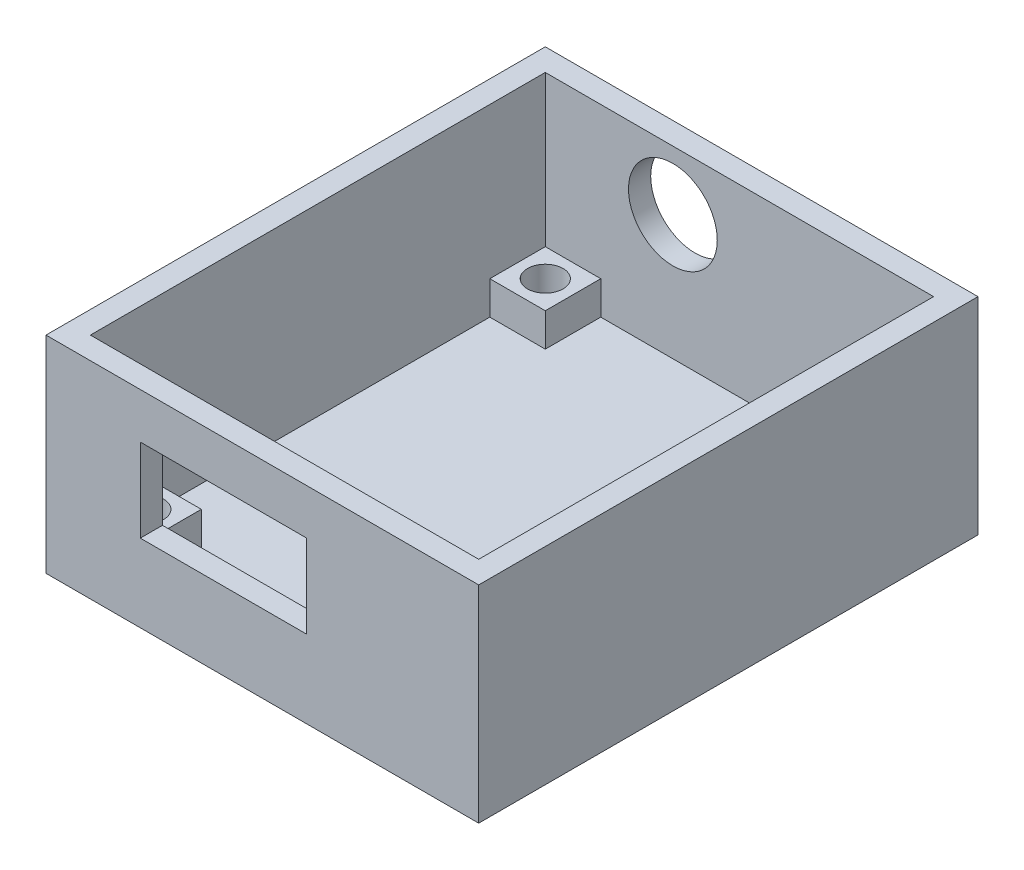
SolidWorks part; units mm, degrees
ref_plane "Front Plane" through (0, 0, 0) normal (0, 0, 1) x (1, 0, 0)
ref_plane "Top Plane" through (0, 0, 0) normal (0, 1, 0) x (1, 0, 0)
ref_plane "Right Plane" through (0, 0, 0) normal (1, 0, 0) x (0, 0, -1)
sketch "Sketch1" plane through (0, 0, 0) normal (0, 1, 0) x (1, 0, 0)
  line L1 (19.5, -22.5) -> (-19.5, -22.5)
  line L2 (19.5, -22.5) -> (19.5, 22.5)
  line L3 (19.5, 22.5) -> (-19.5, 22.5)
  line L4 (-19.5, -22.5) -> (-19.5, 22.5)
  line L5 (19.5, -22.5) -> (-19.5, 22.5) construction
  line L6 (19.5, 22.5) -> (-19.5, -22.5) construction
  point P0 (0, 0)
  dimension "D1" = 45
  dimension "D2" = 39
extrude "Body" add sketch "Sketch1" along normal blind 18.6
shell "Shell1" thickness 2 removed face at (0, 18.6, 0)
sketch "Sketch3" plane through (0, 2, 0) normal (0, 1, 0) x (1, 0, 0)
  line L0 (-1000, 0) -> (49000, 0) construction
  line L5 (-17.5, 20.5) -> (-12.5, 20.5)
  line L6 (-17.5, 20.5) -> (-17.5, 15.5)
  line L7 (-17.5, 15.5) -> (-12.5, 15.5)
  line L8 (-12.5, 20.5) -> (-12.5, 15.5)
  line L9 (0, -1000) -> (0, 49000) construction
  line L10 (12.5, 20.5) -> (12.5, 15.5)
  line L11 (17.5, 15.5) -> (12.5, 15.5)
  line L12 (17.5, 20.5) -> (17.5, 15.5)
  line L13 (17.5, 20.5) -> (12.5, 20.5)
  line L14 (17.5, -20.5) -> (12.5, -20.5)
  line L15 (17.5, -20.5) -> (17.5, -15.5)
  line L16 (17.5, -15.5) -> (12.5, -15.5)
  line L17 (12.5, -20.5) -> (12.5, -15.5)
  line L18 (-12.5, -20.5) -> (-12.5, -15.5)
  line L19 (-17.5, -15.5) -> (-12.5, -15.5)
  line L20 (-17.5, -20.5) -> (-17.5, -15.5)
  line L21 (-17.5, -20.5) -> (-12.5, -20.5)
  dimension "D1" = 5
extrude "Inserts_Support" add sketch "Sketch3" along normal blind 3
sketch "Sketch4" plane through (0, 5, 0) normal (0, 1, 0) x (1, 0, 0)
  line L1 (15, -18) -> (-15, -18) construction
  line L2 (15, -18) -> (15, 18) construction
  line L3 (15, 18) -> (-15, 18) construction
  line L4 (-15, -18) -> (-15, 18) construction
  line L5 (15, -18) -> (-15, 18) construction
  line L6 (15, 18) -> (-15, -18) construction
  circle A0 centre (-15, 18) radius 1.6
  circle A1 centre (15, 18) radius 1.6
  circle A2 centre (15, -18) radius 1.6
  circle A3 centre (-15, -18) radius 1.6
  point P0 (0, 0)
  dimension "D3" = 3.2
  dimension "D1" = 30
  dimension "D2" = 36
extrude "Inserts_Holes" cut sketch "Sketch4" against normal blind 4
sketch "Sketch5" plane through (0, 0, 22.5) normal (0, 0, 1) x (1, 0, 0)
  line L0 (-19.5, 18.6) -> (-19.5, 0) construction
  line L1 (-11, 14.5) -> (4, 14.5)
  line L2 (-11, 14.5) -> (-11, 7)
  line L3 (-11, 7) -> (4, 7)
  line L4 (4, 14.5) -> (4, 7)
  line L5 (-11, 14.5) -> (4, 7) construction
  line L6 (-11, 7) -> (4, 14.5) construction
  point P0 (-3.5, 10.75)
  dimension "D1" = 7.5
  dimension "15" = 15
  dimension "D2" = 8.5
  dimension "D3" = 7
extrude "USB_Hole" cut sketch "Sketch5" against normal up to next
sketch "Sketch6" plane through (0, 0, -22.5) normal (0, 0, -1) x (-1, 0, 0)
  line L0 (19.5, 18.6) -> (19.5, 0) construction
  circle A0 centre (6, 13.25) radius 4
  dimension "D1" = 8
  dimension "D2" = 13.25
  dimension "D3" = 13.5
extrude "Jack_Hole" cut sketch "Sketch6" against normal up to next
